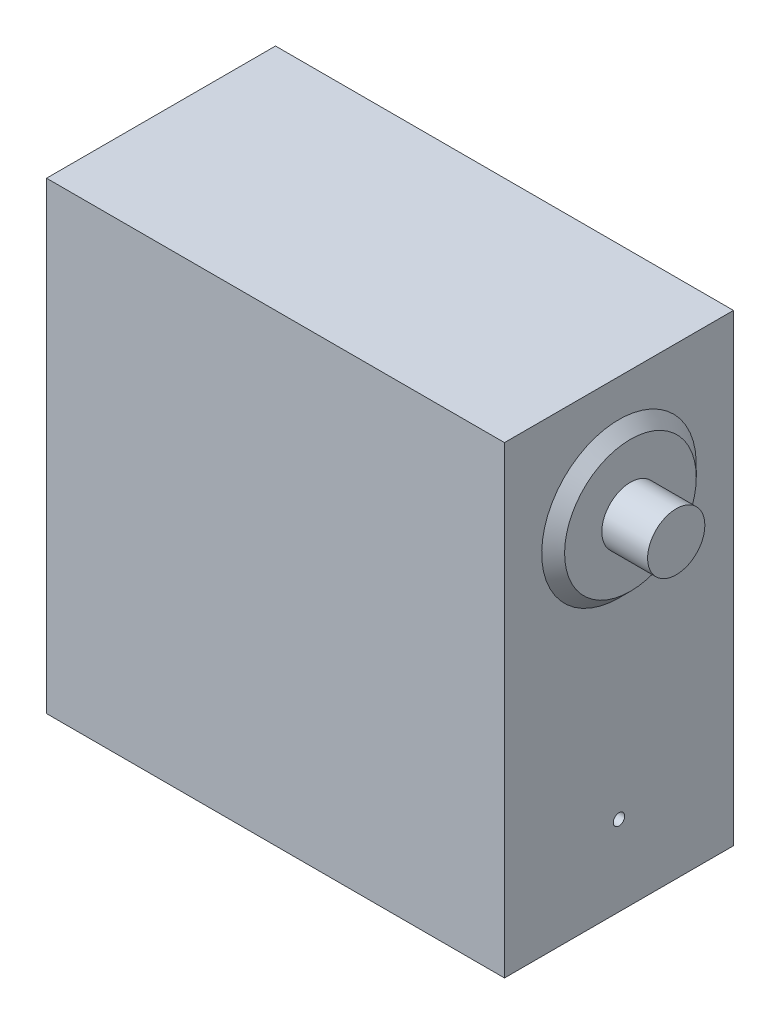
SolidWorks part; units mm, degrees
ref_plane "前视基准面" through (0, 0, 0) normal (0, 0, 1) x (1, 0, 0)
ref_plane "上视基准面" through (0, 0, 0) normal (0, 1, 0) x (1, 0, 0)
ref_plane "右视基准面" through (0, 0, 0) normal (1, 0, 0) x (0, 0, -1)
sketch "草图1" plane through (0, 0, 0) normal (0, 0, 1) x (1, 0, 0)
  line L1 (-20, 20.25) -> (20, 20.25)
  line L2 (-20, 20.25) -> (-20, -20.25)
  line L3 (-20, -20.25) -> (20, -20.25)
  line L4 (20, 20.25) -> (20, -20.25)
  dimension "D1" = 40
  dimension "D2" = 40.5
  dimension "D3" = 20
  dimension "D4" = 20.25
extrude "凸台-拉伸1" add sketch "草图1" along normal mid plane 20
sketch "草图3" plane through (20, 0, 0) normal (1, 0, 0) x (0, 0, -1)
  line L0 (-10, 20.25) -> (10, 20.25) construction
  circle A0 centre (0, 10.25) radius 6.75
  dimension "D1" = 13.5
  dimension "D2" = 10
extrude "凸台-拉伸2" add sketch "草图3" along normal blind 1
sketch "草图4" plane through (21, 0, 0) normal (1, 0, 0) x (0, 0, -1)
  circle A0 centre (0, 10.25) radius 2.5
  circle A1 centre (0, 10.25) radius 6.75 construction
  dimension "D1" = 5
extrude "凸台-拉伸3" add sketch "草图4" along normal blind 4
sketch "草图5" plane through (-20, 0, 0) normal (-1, 0, 0) x (0, 0, 1)
  line L0 (10, 20.25) -> (-10, 20.25) construction
  circle A0 centre (0, 10.25) radius 6.75
  dimension "D1" = 13.5
  dimension "D2" = 10
extrude "凸台-拉伸4" add sketch "草图5" along normal blind 2
sketch "草图6" plane through (-22, 0, 0) normal (-1, 0, 0) x (0, 0, 1)
  circle A0 centre (0, 10.25) radius 1.75
  dimension "D1" = 3.5
extrude "切除-拉伸1" cut sketch "草图6" against normal blind 4
sketch "草图7" plane through (-20, 0, 0) normal (-1, 0, 0) x (0, 0, 1)
  line L4 (-10, 20.25) -> (-10, -20.25)
  line L5 (-10, -20.25) -> (10, -20.25)
  line L6 (10, -20.25) -> (10, 20.25)
  line L7 (10, 20.25) -> (-10, 20.25)
  line L8 (-10, 20.25) -> (-10, -20.25)
  line L9 (-10, -20.25) -> (10, -20.25)
  line L10 (10, -20.25) -> (10, 20.25)
  line L11 (10, 20.25) -> (-10, 20.25)
  circle A0 centre (-8, -8.25) radius 0.5
  circle A1 centre (8, -8.25) radius 0.5
  circle A2 centre (8, -18.25) radius 0.5
  circle A3 centre (-8, -18.25) radius 0.5
  dimension "D2" = 1
  dimension "D3" = 1
  dimension "D4" = 1
  dimension "D5" = 1
  dimension "D6" = 2
  dimension "D7" = 2
  dimension "D8" = 2
  dimension "D9" = 2
  dimension "D10" = 2
  dimension "D11" = 2
  dimension "D12" = 10
  dimension "D13" = 10
  dimension "D1" = 0
extrude "切除-拉伸3" cut sketch "草图7" against normal blind 4 contours A0 | A3 | A1 | A2
sketch "草图8" plane through (20, 0, 0) normal (1, 0, 0) x (0, 0, -1)
  line L0 (-10, -20.25) -> (10, -20.25) construction
  circle A0 centre (0, -13.25) radius 0.5
  dimension "D1" = 1
  dimension "D2" = 7
extrude "切除-拉伸4" cut sketch "草图8" against normal blind 4
chamfer "倒角1" distance 1 1 edges at (21, 17, 0)
sketch "草图9" plane through (0, 0, -10) normal (0, 0, -1) x (-1, 0, 0)
  text T0 "RDS3115"
  text T1 "MG" font "汉仪长仿宋体" height 1.5
extrude "切除-拉伸5" cut sketch "草图9" against normal blind 1
